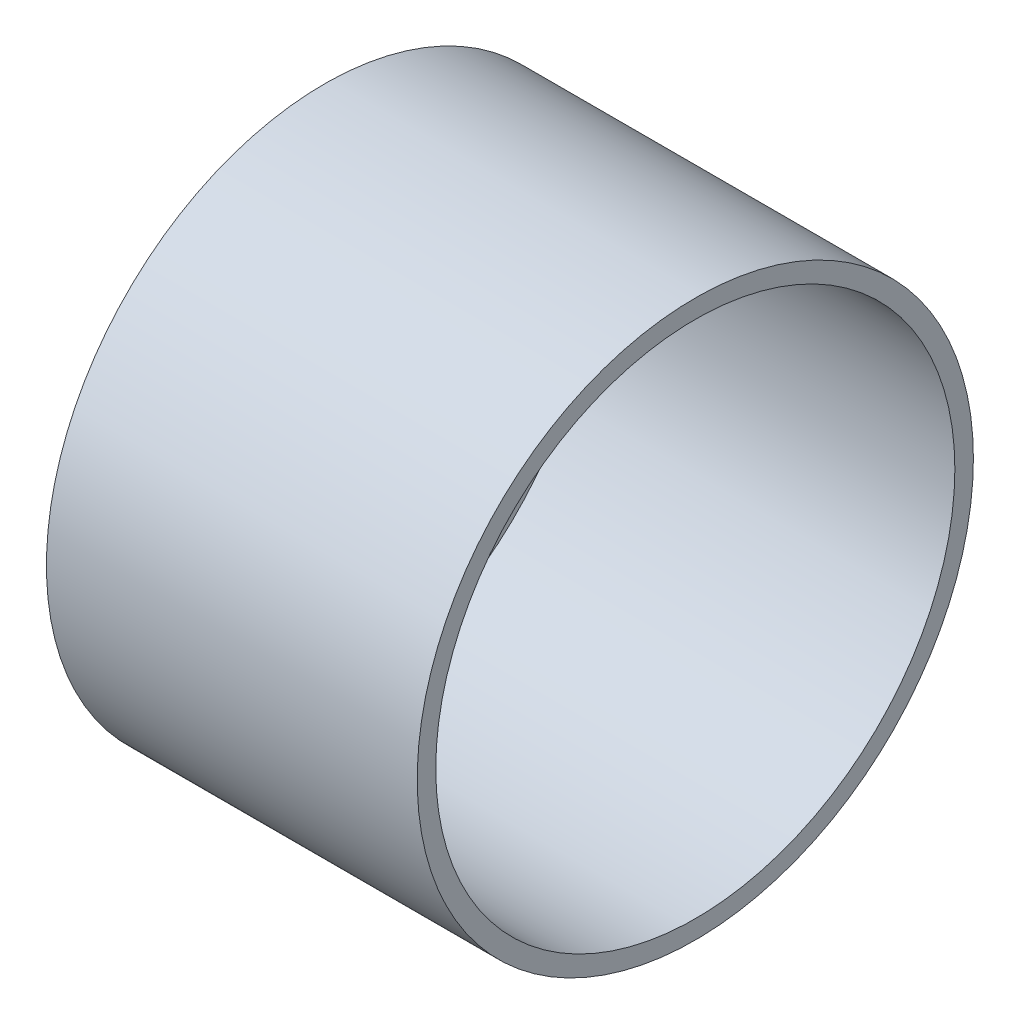
SolidWorks part; units mm, degrees
note: The reader was unsure of these and kept them because the rebuilt part matched: shared geometry of "Sketch1<4>".
ref_plane "Front Plane" through (0, 0, 0) normal (0, 0, 1) x (1, 0, 0)
ref_plane "Top Plane" through (0, 0, 0) normal (0, 1, 0) x (1, 0, 0)
ref_plane "Right Plane" through (0, 0, 0) normal (1, 0, 0) x (0, 0, -1)
sketch "Sketch1" plane through (0, 0, 0) normal (1, 0, 0) x (0, 0, -1)
  circle A0 centre (0, 0) radius 75
  circle A1 centre (0, 0) radius 70
  dimension "D1" = 150
  dimension "D2" = 140
extrude "Boss-Extrude1" add sketch "Sketch1" along normal blind 2 contours A1
extrude "Boss-Extrude2" add sketch "Sketch1<4>" along normal blind 100
sketch "Sketch1<4>" plane through (0, 0, 0) normal (1, 0, 0) x (0, 0, -1) same geometry as "Sketch1"
sketch "Sketch2" plane through (0, 0, 0) normal (-1, 0, 0) x (0, 0, 1)
  circle A0 centre (0, 0) radius 65
  dimension "D1" = 130
sketch "Sketch4" plane through (2, 0, 0) normal (1, 0, 0) x (0, 0, -1)
  line L0 (0, 0) -> (0, 15) construction
  line L1 (0, 0) -> (-12.9904, -7.5) construction
  line L2 (0, 0) -> (12.9904, -7.5) construction
  circle A0 centre (0, 0) radius 15 construction
  point P3 (0, 15)
  point P4 (-12.9904, -7.5)
  point P5 (12.9904, -7.5)
  point P13 (0, 0)
  dimension "D1" = 30
  dimension "D2" = 120
  dimension "D3" = 120
hole_wizard "M3 Clearance Hole1" positions "Sketch4" profile "Sketch9" hole size "M3" standard "AS"
sketch "Sketch9" plane through (2, -7.5, -12.9904) normal (0, 1, 0) x (0, 0, -1)
  line L0 (0, 0) -> (0, 3.0815)
  line L1 (0, 3.0815) -> (1.8, 2)
  line L2 (1.8, 2) -> (1.8, 0)
  line L5 (1.8, 0) -> (0, 0)
  line L10 (0, 3.0815) -> (-1.8, 2) construction
  line L11 (0, -6.35) -> (0, 107.95) construction
  dimension "Hole Dia." = 3.6
  dimension "Hole Depth" = 2
  dimension "Drill Angle" = 118
sketch "Sketch11" plane through (2, 0, 0) normal (1, 0, 0) x (0, 0, -1)
  point P0 (0, 0)
  point P3 (0, 0)
hole_wizard "M10 Clearance Hole1" positions "Sketch11" profile "Sketch12" hole size "M10" standard "AS"
sketch "Sketch12" plane through (2, 0, 0) normal (0, 1, 0) x (0, 0, -1)
  line L0 (0, 0) -> (0, 5.6052)
  line L1 (0, 5.6052) -> (6, 2)
  line L2 (6, 2) -> (6, 0)
  line L5 (6, 0) -> (0, 0)
  line L10 (0, 5.6052) -> (-6, 2) construction
  line L11 (0, -6.35) -> (0, 107.95) construction
  dimension "Hole Dia." = 12
  dimension "Hole Depth" = 2
  dimension "Drill Angle" = 118
